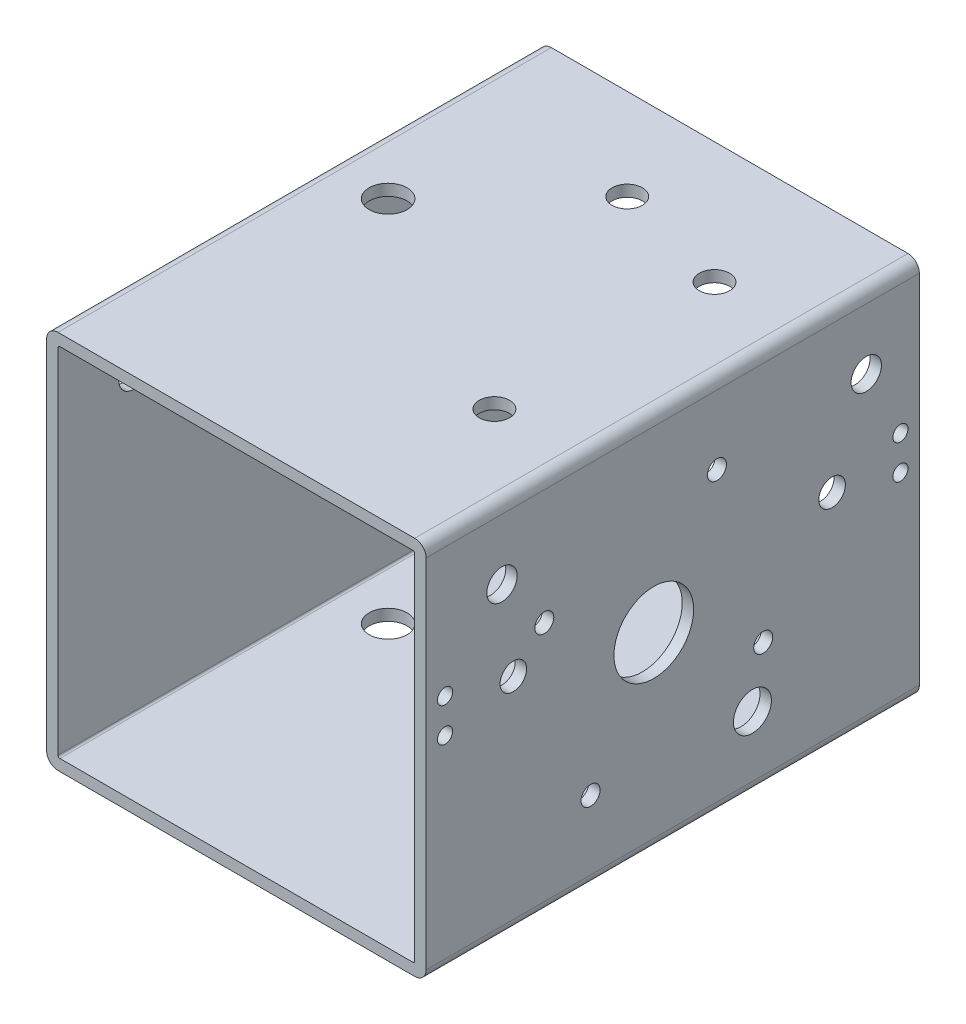
SolidWorks part; units mm, degrees
ref_plane "Front Plane" through (0, 0, 0) normal (0, 0, 1) x (1, 0, 0)
ref_plane "Top Plane" through (0, 0, 0) normal (0, 1, 0) x (1, 0, 0)
ref_plane "Right Plane" through (0, 0, 0) normal (1, 0, 0) x (0, 0, -1)
sketch "Sketch1" plane through (0, 0, 0) normal (0, 0, 1) x (1, 0, 0)
  line L1 (-50, 50) -> (50, 50)
  line L2 (-50, 50) -> (-50, -50)
  line L3 (-50, -50) -> (50, -50)
  line L4 (50, 50) -> (50, -50)
  line L5 (-50, 50) -> (50, -50) construction
  line L6 (-50, -50) -> (50, 50) construction
  point P0 (0, 0)
  dimension "D1" = 100
  dimension "D2" = 100
extrude "Extrude-Thin1" add sketch "Sketch1" along normal blind 130 thin thin type one direction reverse wall 3
fillet "Fillet1" radius 0.5 4 edges at (-47, -47, 65) (-47, 47, 65) (47, 47, 65) (47, -47, 65)
fillet "Fillet2" radius 3 4 edges at (50, -50, 65) (-50, -50, 65) (50, 50, 65) (-50, 50, 65)
sketch "Holes - top" plane through (0, 0, 0) normal (0, 1, 0) x (1, 0, 0)
  line L0 (-3, 0) -> (-3, -130) construction
  line L1 (47, -130) -> (-47, -130) construction
  line L2 (-23, 0) -> (-23, -130) construction
  line L3 (47, 0) -> (-47, 0) construction
  line L4 (17, 0) -> (17, -130) construction
  circle A0 centre (-34, -56) radius 11 construction
  circle A1 centre (28, -90) radius 11 construction
  circle A2 centre (28, -32) radius 11 construction
  dimension "D4" = 22
  dimension "D1" = 40
  dimension "D2" = 40
  dimension "D3" = 32
  dimension "D5" = 56
  dimension "D6" = 3
hole_wizard "Ø8.0 (8) Diameter Hole2" positions "Sketch6" profile "Sketch5" hole size "Ø8.0" standard "ANSI Metric" end condition through all
sketch "Sketch6" plane through (0, 50, 0) normal (0, 1, 0) x (1, 0, 0)
  point P0 (28, -32)
  point P6 (28, -90)
sketch "Sketch5" plane through (28, 50, 32) normal (1, 0, 0) x (0, 0, 1)
  line L0 (0, 0) -> (0, 100)
  line L1 (0, 100) -> (4, 100)
  line L2 (4, 100) -> (4, 0)
  line L5 (4, 0) -> (0, 0)
  line L11 (0, -6.35) -> (0, 107.95) construction
  dimension "Thru Hole Dia." = 8
  dimension "Thru Hole Depth" = 100
sketch "Holes - side" plane through (0, 0, 0) normal (1, 0, 0) x (0, 0, -1)
  line L0 (0, 0) -> (-130, 0) construction
  line L1 (-130, -47) -> (-130, 47) construction
  line L2 (-130, 20) -> (0, 20) construction
  line L3 (0, -47) -> (0, 47) construction
  line L4 (-130, -20) -> (0, -20) construction
  circle A0 centre (-110, 31) radius 11 construction
  circle A1 centre (-14, 31) radius 11 construction
  circle A2 centre (-44, -31) radius 11 construction
  dimension "D1" = 40
  dimension "D2" = 22
  dimension "D3" = 20
  dimension "D4" = 14
  dimension "D5" = 44
hole_wizard "Ø8.0 (8) Diameter Hole3" positions "Sketch9" profile "Sketch8" hole size "Ø8.0" standard "ANSI Metric" end condition through all
sketch "Sketch9" plane through (50, 0, 0) normal (1, 0, 0) x (0, 0, -1)
  point P0 (-14, 31)
  point P3 (-110, 31)
sketch "Sketch8" plane through (50, 31, 14) normal (0, 1, 0) x (0, 0, -1)
  line L0 (0, 0) -> (0, 100)
  line L1 (0, 100) -> (4, 100)
  line L2 (4, 100) -> (4, 0)
  line L5 (4, 0) -> (0, 0)
  line L11 (0, -6.35) -> (0, 107.95) construction
  dimension "Thru Hole Dia." = 8
  dimension "Thru Hole Depth" = 100
hole_wizard "Ø10.0 (10) Diameter Hole1" positions "Sketch12" profile "Sketch11" hole size "Ø10.0" standard "ANSI Metric" end condition through all
sketch "Sketch12" plane through (0, 50, 0) normal (0, 1, 0) x (1, 0, 0)
  point P0 (-34, -56)
sketch "Sketch11" plane through (-34, 50, 56) normal (1, 0, 0) x (0, 0, 1)
  line L0 (0, 0) -> (0, 100)
  line L1 (0, 100) -> (5, 100)
  line L2 (5, 100) -> (5, 0)
  line L5 (5, 0) -> (0, 0)
  line L11 (0, -6.35) -> (0, 107.95) construction
  dimension "Thru Hole Dia." = 10
  dimension "Thru Hole Depth" = 100
hole_wizard "Ø10.0 (10) Diameter Hole2" positions "Sketch14" profile "Sketch13" hole size "Ø10.0" standard "ANSI Metric" end condition through all
sketch "Sketch14" plane through (50, 0, 0) normal (1, 0, 0) x (0, 0, -1)
  point P0 (-44, -31)
sketch "Sketch13" plane through (50, -31, 44) normal (0, 1, 0) x (0, 0, -1)
  line L0 (0, 0) -> (0, 100)
  line L1 (0, 100) -> (5, 100)
  line L2 (5, 100) -> (5, 0)
  line L5 (5, 0) -> (0, 0)
  line L11 (0, -6.35) -> (0, 107.95) construction
  dimension "Thru Hole Dia." = 10
  dimension "Thru Hole Depth" = 100
hole_wizard "M8x1.25 Tapped Hole1" positions "Sketch18" profile "Sketch17" tap size "M8x1.25" standard "ANSI Metric" end condition up to next
sketch "Sketch18" plane through (-50, 0, 0) normal (-1, 0, 0) x (0, 0, 1)
  line L0 (56, 35) -> (56, -15) construction
  point P0 (56, -15)
  point P2 (56, 35)
  dimension "D1" = 56
  dimension "D2" = 35
  dimension "D3" = 15
sketch "Sketch17" plane through (-50, -15, 56) normal (0, 1, 0) x (0, 0, 1)
  line L0 (0, 0) -> (0, 3)
  line L1 (0, 3) -> (3.4, 3)
  line L2 (3.4, 3) -> (3.4, 0)
  line L5 (3.4, 0) -> (0, 0)
  line L11 (0, -6.35) -> (0, 107.95) construction
  dimension "Thru Tap Drill Dia." = 6.8
  dimension "Thru Tap Drill Depth" = 3
cosmetic thread "Hole Thread1" parameters "D2"=8
cosmetic thread "Hole Thread2" parameters "D2"=8
hole_wizard "M8x1.25 Tapped Hole2" positions "Sketch21" profile "Sketch20" tap size "M8x1.25" standard "ANSI Metric" end condition up to next
sketch "Sketch21" plane through (0, -50, 0) normal (0, -1, 0) x (-1, 0, 0)
  line L0 (20, -44) -> (-35, -44) construction
  point P0 (20, -44)
  point P2 (-35, -44)
  dimension "D1" = 44
  dimension "D2" = 35
  dimension "D3" = 20
sketch "Sketch20" plane through (-20, -50, 44) normal (1, 0, 0) x (0, 0, -1)
  line L0 (0, 0) -> (0, 3)
  line L1 (0, 3) -> (3.4, 3)
  line L2 (3.4, 3) -> (3.4, 0)
  line L5 (3.4, 0) -> (0, 0)
  line L11 (0, -6.35) -> (0, 107.95) construction
  dimension "Thru Tap Drill Dia." = 6.8
  dimension "Thru Tap Drill Depth" = 3
cosmetic thread "Hole Thread3" parameters "D2"=8
cosmetic thread "Hole Thread4" parameters "D2"=8
sketch "Holes - Nema 23 motor" plane through (0, 0, 0) normal (1, 0, 0) x (0, 0, -1)
  line L0 (-98.8427, 16.6524) -> (-53.3476, 28.8427) construction
  line L1 (-98.8427, 16.6524) -> (-86.6524, -28.8427) construction
  line L2 (-53.3476, 28.8427) -> (-41.1573, -16.6524) construction
  line L3 (-86.6524, -28.8427) -> (-41.1573, -16.6524) construction
  line L4 (-98.8427, 16.6524) -> (-41.1573, -16.6524) construction
  line L5 (-53.3476, 28.8427) -> (-86.6524, -28.8427) construction
  line L6 (0, 0) -> (-130, 0) construction
  point P1 (-70, 0)
  dimension "D1" = 70
  dimension "D2" = 47.1
  dimension "D3" = 47.1
  dimension "D4" = 15
hole_wizard "Ø21.0 (21) Diameter Hole1" positions "Sketch24" profile "Sketch23" hole size "Ø21.0" standard "ANSI Metric" end condition up to next
sketch "Sketch24" plane through (50, 0, 0) normal (1, 0, 0) x (0, 0, -1)
  point P0 (-70, 0)
sketch "Sketch23" plane through (50, 0, 70) normal (0, 1, 0) x (0, 0, -1)
  line L0 (0, 0) -> (0, 3)
  line L1 (0, 3) -> (10.5, 3)
  line L2 (10.5, 3) -> (10.5, 0)
  line L5 (10.5, 0) -> (0, 0)
  line L11 (0, -6.35) -> (0, 107.95) construction
  dimension "Thru Hole Dia." = 21
  dimension "Thru Hole Depth" = 3
hole_wizard "Ø5.0 (5) Diameter Hole1" positions "Sketch26" profile "Sketch25" hole size "Ø5.0" standard "ANSI Metric" end condition up to next
sketch "Sketch26" plane through (50, 0, 0) normal (1, 0, 0) x (0, 0, -1)
  point P0 (-41.1573, -16.6524)
  point P3 (-53.3476, 28.8427)
  point P6 (-98.8427, 16.6524)
  point P9 (-86.6524, -28.8427)
sketch "Sketch25" plane through (50, -16.6524, 41.1573) normal (0, 1, 0) x (0, 0, -1)
  line L0 (0, 0) -> (0, 3)
  line L1 (0, 3) -> (2.5, 3)
  line L2 (2.5, 3) -> (2.5, 0)
  line L5 (2.5, 0) -> (0, 0)
  line L11 (0, -6.35) -> (0, 107.95) construction
  dimension "Thru Hole Dia." = 5
  dimension "Thru Hole Depth" = 3
hole_wizard "Ø8.0 (8) Diameter Hole4" positions "Sketch29" profile "Sketch28" hole size "Ø8.0" standard "ANSI Metric" end condition up to next
sketch "Sketch29" plane through (0, 50, 0) normal (0, 1, 0) x (1, 0, 0)
  line L0 (-3, 0) -> (-3, -130) construction
  point P0 (-3, -24)
  dimension "D2" = 8
sketch "Sketch28" plane through (-3, 50, 24) normal (1, 0, 0) x (0, 0, 1)
  line L0 (0, 0) -> (0, 3)
  line L1 (0, 3) -> (4, 3)
  line L2 (4, 3) -> (4, 0)
  line L5 (4, 0) -> (0, 0)
  line L11 (0, -6.35) -> (0, 107.95) construction
  dimension "Thru Hole Dia." = 8
  dimension "Thru Hole Depth" = 3
sketch "Sketch31" plane through (50, 0, 0) normal (1, 0, 0) x (0, 0, -1)
  line L0 (0, -47) -> (0, 47) construction
  line L1 (-130, 50) -> (0, 50) construction
  line L2 (-65, 117.0212) -> (-65, -118.5233) construction
  line L3 (-130, -47) -> (-130, 47) construction
  circle A0 centre (-5, 4) radius 2
  circle A1 centre (-5, 13) radius 2
  circle A2 centre (-125, 13) radius 2
  circle A3 centre (-125, 4) radius 2
  circle A4 centre (-23, 8.5) radius 3.5
  circle A5 centre (-107, 8.5) radius 3.5
  dimension "D1" = 4
  dimension "D2" = 4
  dimension "D3" = 9
  dimension "D4" = 5
  dimension "D5" = 46
  dimension "D6" = 5
  dimension "D8" = 7
  dimension "D9" = 18
  dimension "D7" = 65
  dimension "D10" = 4.5
extrude "Cut-Extrude1" cut sketch "Sketch31" against normal up to next
equation "\"a\"= \"Trolley Profile@Plasma Beta.Assembly\""
equation "\"b\"= \"Trolley Profile Thickness@Plasma Beta.Assembly\""
equation "\"L\"= 130"
equation "\"D2@Sketch1\"=\"a\""
equation "\"D1@Sketch1\"=\"a\""
equation "\"D1@Extrude-Thin1\"=\"L\""
equation "\"D5@Extrude-Thin1\"=\"b\""
equation "\"D1@Fillet2\"=\"b\""
equation "\"d-bearing\"= 22'diameter of bearing"
equation "\"a-small\"= \"Beam Profile@Plasma Beta.Assembly\"'profile of smaller beam"
equation "\"D4@Holes - top\"=\"d-bearing\""
equation "\"D2@Holes - side\"=\"d-bearing\""
equation "\"D1@Holes - top\"=\"a-small\""
equation "\"D1@Holes - side\"=\"a-small\""
